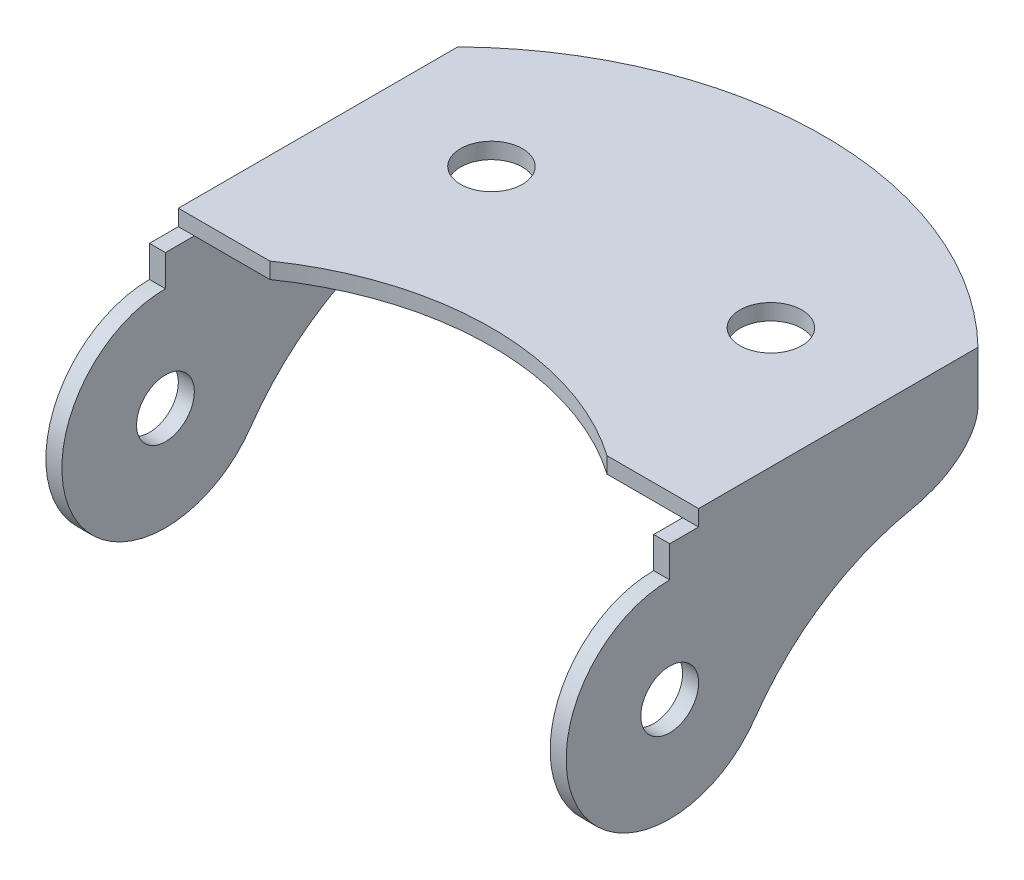
SolidWorks part; units mm, degrees
material "Brass"
ref_plane "Front Plane" through (0, 0, 0) normal (0, 0, 1) x (1, 0, 0)
ref_plane "Top Plane" through (0, 0, 0) normal (0, 1, 0) x (1, 0, 0)
ref_plane "Right Plane" through (0, 0, 0) normal (1, 0, 0) x (0, 0, -1)
sketch "Sketch1" plane through (0, 0, 0) normal (0, 1, 0) x (1, 0, 0)
  line L0 (-7.25, 0) -> (7.25, 0) construction
  line L1 (13.5, 10) -> (8.75, 10)
  line L2 (-13.5, 10) -> (-8.75, 10)
  line L3 (-13.5, 10) -> (-13.5, -10)
  line L4 (-13.5, -10) -> (13.5, -10) construction
  line L5 (13.5, 10) -> (13.5, -10)
  line L6 (-13.5, 10) -> (13.5, -10) construction
  line L7 (-13.5, -10) -> (13.5, 10) construction
  line L8 (-13.5, 10) -> (-8.75, 10)
  line L9 (8.75, 10) -> (13.5, 10)
  circle A0 centre (7.25, 0) radius 1.6066
  circle A1 centre (-7.25, 0) radius 1.6066
  arc A2 (-8.75, 10) -> (8.75, 10) centre (0, 22.5455) ccw
  arc A3 (-13.5, -4.5) -> (13.5, -4.5) centre (0, 9.3182) ccw
  point P4 (0, 0)
  point P7 (0, 0)
  point P15 (0, 7.25)
  point P21 (0, -10)
  dimension "D2" = 3.2131
  dimension "D8" = 5.5
  dimension "D1" = 14.5
  dimension "D3" = 20
  dimension "D4" = 27
  dimension "D5" = 4.75
  dimension "D6" = 4.75
  dimension "D7" = 2.75
  dimension "D9" = 5.5
extrude "Boss-Extrude1" add sketch "Sketch1" along normal blind 0.83 contours L5 L2 L3 L4 A1 A0 region at (0, 0, -0.2203)
sketch "Sketch3" plane through (0, 0, 0) normal (1, 0, 0) x (0, 0, -1)
  line L0 (10, 0.83) -> (-4.5, 0.83)
  line L2 (-4.5, 0.83) -> (11.5, 0.83)
  line L3 (11.5, 0.83) -> (11.5, 2.455)
  line L4 (-4.5, 0.83) -> (-4.5, 5.33)
  line L5 (-4.5, 0.83) -> (-4.5, 0) construction
  line L6 (10, 0.83) -> (-4.5, 0.83) construction
  circle A0 centre (11.5, 7.83) radius 1.5
  arc A1 (11.5, 2.455) -> (7.0827, 10.8923) centre (11.5, 7.83) ccw
  arc A2 (-4.5, 5.33) -> (7.0827, 10.8923) centre (-3.6011, 18.2989) ccw
  dimension "D4" = 3
  dimension "D5" = 10.75
  dimension "D7" = 13
  dimension "D1" = 14.5
  dimension "D2" = 16
  dimension "D3" = 7
  dimension "D6" = 4.5
extrude "Boss-Extrude4" add sketch "Sketch3" against normal blind 0.83 from surface contours A2 L4 L0 L2 L3 A1 A0 region at (0, 5.81, -7.3656) starting at face at (13.5, 0.415, -2.75)
extrude "Boss-Extrude5" add sketch "Sketch3<5>" along normal blind 0.83 from surface contours A2 L4 L0 L2 L3 A1 A0 region at (0, 5.81, -7.3656) starting at face at (-13.5, 0.415, -2.75)
sketch "Sketch3<5>" plane through (0, 0, 0) normal (1, 0, 0) x (0, 0, -1) same geometry as "Sketch3"
fillet "Fillet4" radius 4 1 edges at (-13.085, 5.33, 4.5) second distance 3 first distance on face at (-13.085, 7.3456, -1.659)
fillet "Fillet5" radius 4 1 edges at (13.085, 5.33, 4.5) second distance 3 first distance on face at (13.085, 7.3456, -1.659)
move or copy body "Body-Move/Copy1" bodies to move or copy 105 copy no rotation origin (0, 6.6025, -3.4375) rotation axis (1, 0, 0) rotation angle 180
